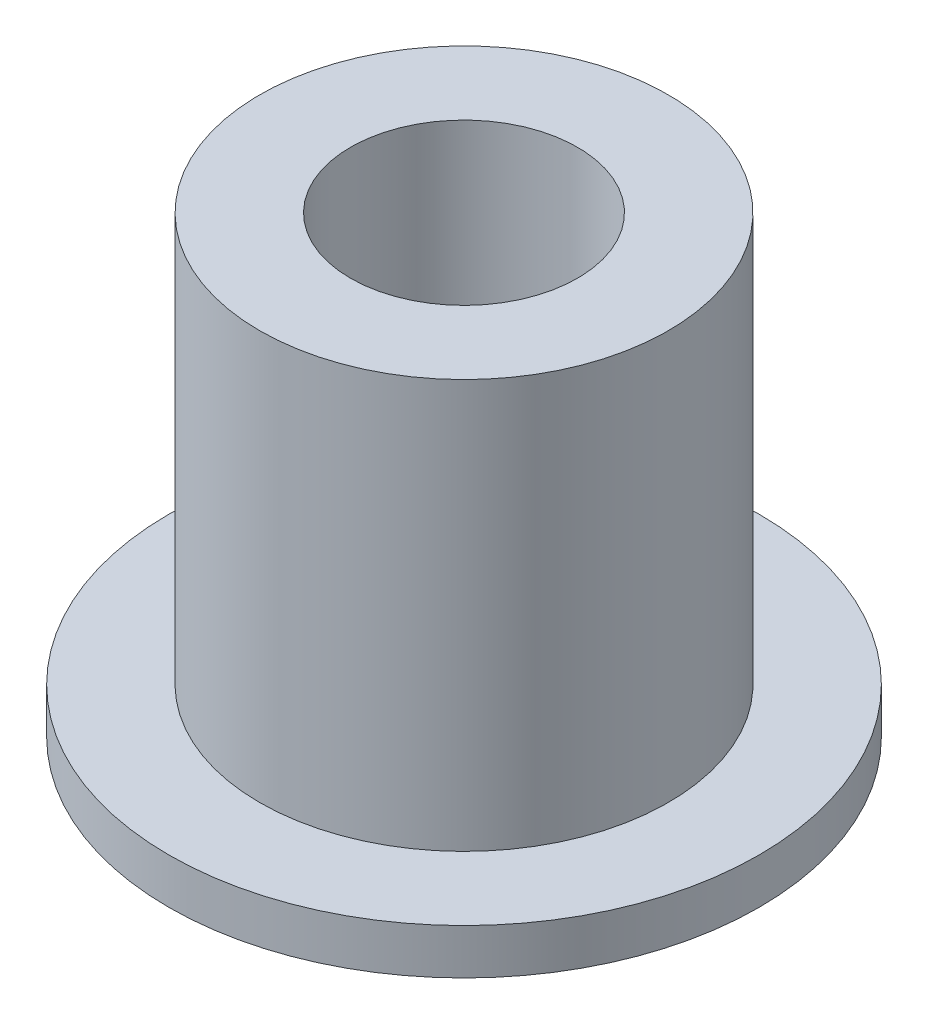
SolidWorks part; units mm, degrees
ref_plane "Front Plane" through (0, 0, 0) normal (0, 0, 1) x (1, 0, 0)
ref_plane "Top Plane" through (0, 0, 0) normal (0, 1, 0) x (1, 0, 0)
ref_plane "Right Plane" through (0, 0, 0) normal (1, 0, 0) x (0, 0, -1)
sketch "Sketch1" plane through (0, 0, 0) normal (0, 1, 0) x (1, 0, 0)
  circle A0 centre (0, 0) radius 2.5
  circle A1 centre (0, 0) radius 4.5
  circle A2 centre (0, 0) radius 6.5
  dimension "D1" = 2
  dimension "D2" = 5
  dimension "D3" = 2
extrude "Boss-Extrude1" add sketch "Sketch1" along normal blind 10 contours A1 A0 region at (-4.3727, 0, 0)
extrude "Boss-Extrude2" add sketch "Sketch1<3>" along normal blind 1 contours A2 A1 region at (-6.3162, 0, 0)
sketch "Sketch1<3>" plane through (0, 0, 0) normal (0, 1, 0) x (1, 0, 0) same geometry as "Sketch1"
